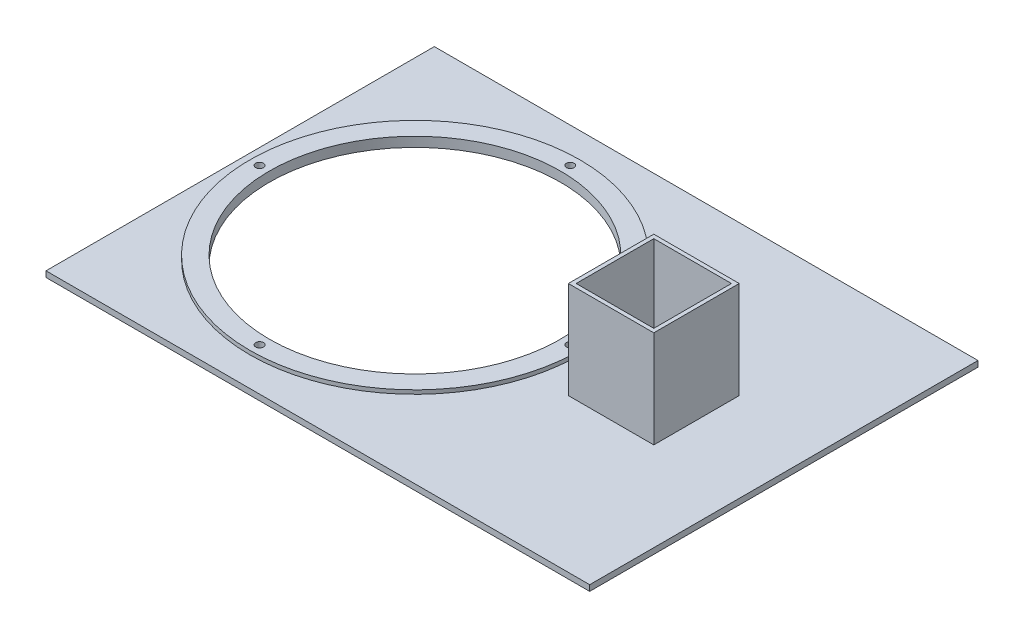
SolidWorks part; units mm, degrees
ref_plane "前视基准面" through (0, 0, 0) normal (0, 0, 1) x (1, 0, 0)
ref_plane "上视基准面" through (0, 0, 0) normal (0, 1, 0) x (1, 0, 0)
ref_plane "右视基准面" through (0, 0, 0) normal (1, 0, 0) x (0, 0, -1)
other "Configuration Table"
sketch "草图1" plane through (0, 0, 0) normal (0, 1, 0) x (1, 0, 0)
  line L0 (140, 0) -> (140, 50000) construction
  line L1 (-140, -100) -> (140, -100)
  line L2 (-140, -100) -> (-140, 100)
  line L3 (-140, 100) -> (140, 100)
  line L4 (140, -100) -> (140, 100)
  line L5 (-140, 100) -> (40, -100) construction
  line L6 (40, 100) -> (-140, -100) construction
  line L8 (-1140, 0) -> (48860, 0) construction
  line L9 (-50, 0) -> (-50, 50000) construction
  line L11 (40, 0) -> (40, 74.2424) construction
  circle A0 centre (-50, 0) radius 75
  circle A1 centre (-50, 0) radius 85
  circle A2 centre (-50, 80) radius 2
  circle A3 centre (-50, -80) radius 2
  circle A4 centre (30, 0) radius 2
  circle A5 centre (-50, -80) radius 2
  circle A6 centre (-130, 0) radius 2
  point P0 (0, 0)
  point P9 (140, 0)
  point P15 (-140, 0)
  dimension "D3" = 150
  dimension "D5" = 90
  dimension "D7" = 80
  dimension "D8" = 4
  dimension "D9" = 4
  dimension "D1" = 280
  dimension "D2" = 200
  dimension "D4" = 190
  dimension "D6" = 10
extrude "凸台-拉伸1" add sketch "草图1" along normal blind 3 contours L1 L4 L3 L2 A1 region at (-136.5591, 0, 0)
extrude "凸台-拉伸3" add sketch "草图1<4>" along normal blind 5 contours A1 A6 A4 A0 A2 A3 region at (-132.5958, 0, 0)
sketch "草图1<4>" plane through (0, 0, 0) normal (0, 1, 0) x (1, 0, 0) same geometry as "草图1"
ref_plane "基准面1" through (0, 3, 0) normal (0, 1, 0) x (1, 0, 0)
sketch "草图2" plane through (0, 3, 0) normal (0, 1, 0) x (1, 0, 0)
  line L0 (50.1751, 22.8486) -> (94.1751, 22.8486)
  line L1 (52.1751, -19.1514) -> (92.1751, -19.1514)
  line L2 (52.1751, -19.1514) -> (52.1751, 20.8486)
  line L3 (52.1751, 20.8486) -> (92.1751, 20.8486)
  line L4 (92.1751, -19.1514) -> (92.1751, 20.8486)
  line L5 (52.1751, -19.1514) -> (92.1751, 20.8486) construction
  line L6 (52.1751, 20.8486) -> (92.1751, -19.1514) construction
  line L7 (94.1751, -21.1514) -> (94.1751, 22.8486)
  line L8 (50.1751, -21.1514) -> (94.1751, -21.1514)
  line L9 (50.1751, -21.1514) -> (50.1751, 22.8486)
  point P0 (72.1751, 0.8486)
  dimension "D1" = 40
  dimension "D2" = 40
  dimension "D3" = 2
extrude "凸台-拉伸4" add sketch "草图2" along normal blind 50
sketch "草图3" plane through (0, 3, 0) normal (0, 1, 0) x (1, 0, 0)
  line L0 (92.1751, 20.8486) -> (52.1751, 20.8486) construction
  line L8 (92.1751, -19.1514) -> (92.1751, 20.8486) construction
  circle A0 centre (72.1751, 0.8486) radius 1
  point P6 (49.117, 16.415)
  dimension "D3" = 2
  dimension "D1" = 20
  dimension "D2" = 20
extrude "切除-拉伸1" cut sketch "草图3" against normal blind 50
